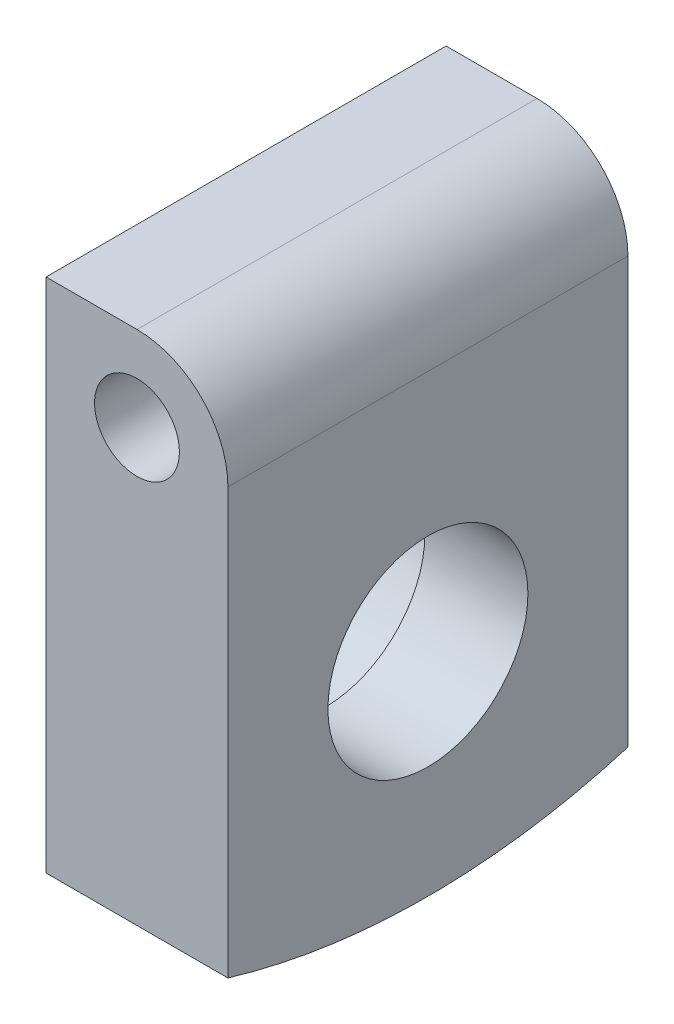
SolidWorks part; units mm, degrees
material "Zinc AC43A (Zn-4Al-2.5Cu-0.04Mg; Number 2 Die Casting Alloy; Zamak 2), Die Cast"
ref_plane "Front Plane" through (0, 0, 0) normal (0, 0, 1) x (1, 0, 0)
ref_plane "Top Plane" through (0, 0, 0) normal (0, 1, 0) x (1, 0, 0)
ref_plane "Right Plane" through (0, 0, 0) normal (1, 0, 0) x (0, 0, -1)
sketch "Sketch1" plane through (0, 0, 0) normal (0, 0, 1) x (1, 0, 0)
  line L1 (0, 0) -> (30, 0)
  line L2 (0, 0) -> (0, 90)
  line L3 (0, 90) -> (15, 90)
  line L4 (30, 0) -> (30, 75)
  arc A1 (15, 90) -> (30, 75) centre (15, 75) cw
  point P7 (30, 90)
  dimension "D3" = 15
  dimension "D1" = 90
  dimension "D2" = 30
extrude "Boss-Extrude1" add sketch "Sketch1" along normal blind 66
sketch "Sketch3" plane through (30, 0, 0) normal (1, 0, 0) x (0, 0, -1)
  line L0 (-66, 90) -> (0, 90) construction
  line L1 (0, 0) -> (0, 75) construction
  circle A0 centre (-33, 35) radius 22.5
  circle A1 centre (-33, 35) radius 16.5
  dimension "D3" = 45
  dimension "D4" = 33
  dimension "D1" = 55
  dimension "D2" = 33
extrude "Cut-Extrude2" cut sketch "Sketch3" against normal blind 13 from offset 17 offset against normal yes
extrude "Cut-Extrude3" cut sketch "Sketch3<2>" against normal up to next contours A1 region at (30, 35, 33)
sketch "Sketch3<2>" plane through (30, 0, 0) normal (1, 0, 0) x (0, 0, -1) same geometry as "Sketch3"
sketch "Sketch6" plane through (0, 0, 0) normal (0, 0, -1) x (-1, 0, 0)
  line L0 (0, 90) -> (0, 4.8365) construction
  line L1 (-15, 90) -> (0, 90) construction
  circle A0 centre (-15, 76) radius 6
  dimension "D3" = 12
  dimension "D1" = 15
  dimension "D2" = 14
sketch "Sketch7" plane through (0, 0, 66) normal (0, 0, 1) x (1, 0, 0)
  circle A0 centre (15, 76) radius 7
  dimension "D1" = 14
loft "Cut-Loft1" cut profiles "Sketch7", "Sketch6" connector at (8.1042, 77.2035, 66) connector at (9.1254, 74.7796, 0)
sketch "Sketch8" plane through (0, 0, 0) normal (-1, 0, 0) x (0, 0, 1)
  line L0 (0, 90) -> (0, 0) construction
  line L1 (66, 90) -> (66, 0) construction
  line L2 (66, 0) -> (0, 0) construction
  line L3 (0, 4.8365) -> (0, 0)
  line L4 (0, 0) -> (66, 0)
  line L5 (66, 0) -> (66, 4.8365)
  arc A0 (0, 4.8365) -> (66, 4.8365) centre (33, 115) ccw
  line M2 (0, 90) -> (0, 0)
  line M3 (0, 0) -> (66, 0)
  line M4 (66, 0) -> (66, 90)
  dimension "D1" = 115
extrude "Cut-Extrude5" cut sketch "Sketch8" against normal through all contours A0 M2 M3 | A0 L4 M4 region at (0, 1.4456, 8.2149) region at (0, 1.4456, 57.7851)
